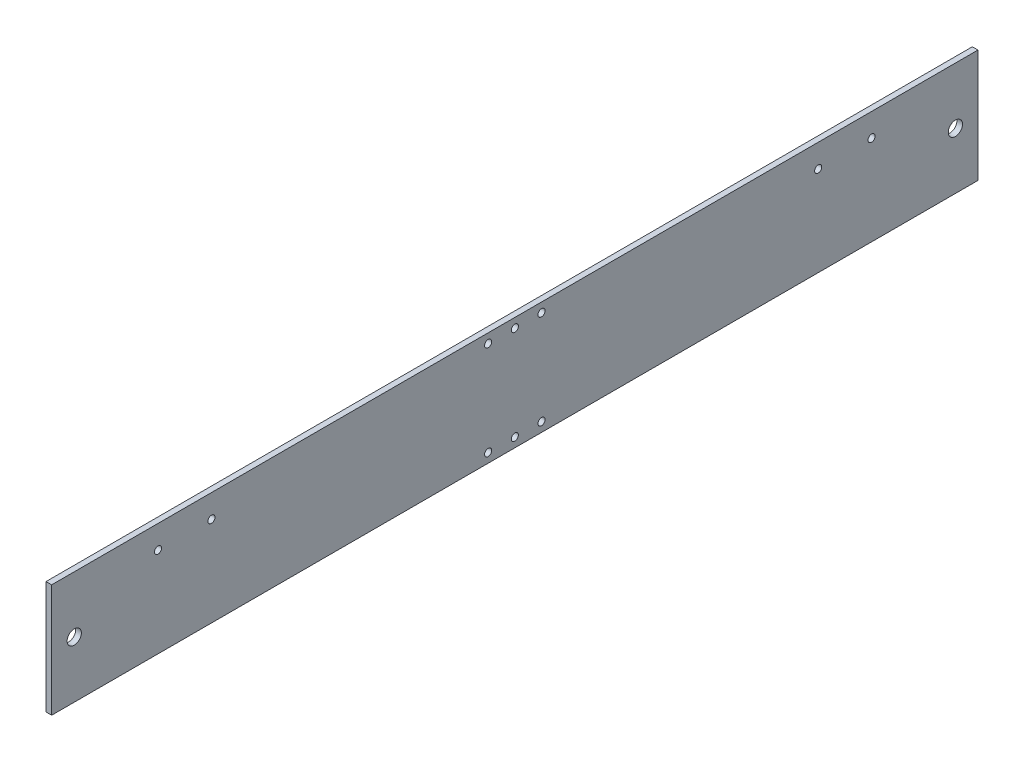
SolidWorks part; units mm, degrees
ref_plane "Front Plane" through (0, 0, 0) normal (0, 0, 1) x (1, 0, 0)
ref_plane "Top Plane" through (0, 0, 0) normal (0, 1, 0) x (1, 0, 0)
ref_plane "Right Plane" through (0, 0, 0) normal (1, 0, 0) x (0, 0, -1)
sketch "Sketch1" plane through (0, 0, 0) normal (1, 0, 0) x (0, 0, -1)
  line L1 (0, 0) -> (520.7, 0)
  line L2 (0, 0) -> (0, 63.5)
  line L3 (0, 63.5) -> (520.7, 63.5)
  line L4 (520.7, 0) -> (520.7, 63.5)
  circle A0 centre (12.7, 31.75) radius 4
  circle A1 centre (508, 31.75) radius 4
  circle A2 centre (245.35, 58.25) radius 2
  circle A7 centre (245.35, 5.25) radius 2
  circle A8 centre (260.35, 58.25) radius 2
  circle A9 centre (275.35, 58.25) radius 2
  circle A10 centre (260.35, 5.25) radius 2
  circle A11 centre (275.35, 5.25) radius 2
  circle A12 centre (59.825, 50.5) radius 2
  circle A13 centre (460.875, 50.5) radius 2
  circle A14 centre (89.825, 50.5) radius 2
  circle A15 centre (430.875, 50.5) radius 2
  dimension "D3" = 8
  dimension "D12" = 4
  dimension "D21" = 4
  dimension "D2" = 520.7
  dimension "D4" = 31.75
  dimension "D5" = 12.7
  dimension "D6" = 12.7
  dimension "D1" = 63.5
  dimension "D7" = 15
  dimension "D8" = 15
  dimension "D9" = 260.35
  dimension "D10" = 5.25
  dimension "D11" = 53
  dimension "D13" = 245.35
  dimension "D14" = 58.25
  dimension "D15" = 260.35
  dimension "D16" = 275.35
  dimension "D17" = 508
  dimension "D18" = 59.825
  dimension "D19" = 59.825
  dimension "D20" = 13
  dimension "D24" = 30
  dimension "D23" = 30
  dimension "D25" = 89.825
  dimension "D26" = 430.875
  dimension "D27" = 460.875
extrude "Boss-Extrude2" add sketch "Sketch1" along normal blind 3.175
equation "\"RailThickness\"= .125in'Spec"
equation "\"VSWidth\"= 1.25in'Spec"
equation "\"StepperHolePadSize\"= \"StepperHoleDiameter\""
equation "\"D2@Sketch1\"= \"FrontOrBackRailLength\""
equation "\"FrameFastenerHoleDiameter\"= 8mm"
equation "\"D3@Sketch1\"=\"FrameFastenerHoleDiameter\""
equation "\"D5@Sketch1\"=\"FrameFastenerHoleOffsetFromEdge\""
equation "\"D6@Sketch1\"=\"FrameFastenerHoleOffsetFromEdge\""
equation "\"D1@Boss-Extrude2\"=\"RailThickness\""
equation "\"FrontOrBackRailLength\"= 20.5in"
equation "\"FrameFastenerHoleOffsetFromEdge\"= \"VSWidth\" / 2 - \"GapBetweenVerticalSupportsAndRails\" / 2"
equation "\"UpperBackRailHeight\"= 2.5in"
equation "\"D4@Sketch1\"=\"UpperBackRailHeight\" /2"
equation "\"D1@Sketch1\"=\"UpperBackRailHeight\""
equation "\"GapBetweenVerticalSupportsAndRails\"= \"RailThickness\" * 2"
equation "\"ExtruderHorizontalMountHolesDistance\"= 15mm'Spec"
equation "\"ExtruderVerticalMountHolesDistance\"= 53mm'Spec"
equation "\"ExtruderMountHolesDiameter\"= 4mm"
equation "\"D7@Sketch1\"=\"ExtruderHorizontalMountHolesDistance\""
equation "\"D8@Sketch1\"=\"ExtruderHorizontalMountHolesDistance\""
equation "\"D9@Sketch1\"=\"FrontOrBackRailLength\"/2"
equation "\"D10@Sketch1\"=(\"UpperBackRailHeight\" - \"ExtruderVerticalMountHolesDistance\")/2"
equation "\"D11@Sketch1\"=\"ExtruderVerticalMountHolesDistance\""
equation "\"D12@Sketch1\"=\"ExtruderMountHolesDiameter\""
equation "\"AngleBracketSmallHoleDiameter\"= 4mm"
equation "\"D21@Sketch1\"=\"AngleBracketSmallHoleDiameter\""
equation "\"AngleBracketSlotDistanceBetweenHoles\"= 30mm"
equation "\"D24@Sketch1\"=\"AngleBracketSlotDistanceBetweenHoles\""
equation "\"D23@Sketch1\"=\"AngleBracketSlotDistanceBetweenHoles\""
equation "\"AngleBracketSlotDistanceFromTop\"= 13mm"
equation "\"D20@Sketch1\"=\"AngleBracketSlotDistanceFromTop\""
equation "\"AngleBracketSlotDistanceFromCorner\"= \"AngleBracketSlotDistanceFromBack\" - \"GapBetweenVerticalSupportsAndRails\" / 2'Equals 61.825"
equation "\"D19@Sketch1\"= \"AngleBracketSlotDistanceFromCorner\" - 2mm 'Minus 2mm to get screw hole in middle of slot"
equation "\"D18@Sketch1\"= \"AngleBracketSlotDistanceFromCorner\" - 2mm'Minus 2mm to get screw hole in middle of slot"
equation "\"AngleBracketSlotDistanceFromBack\"= 65mm"
